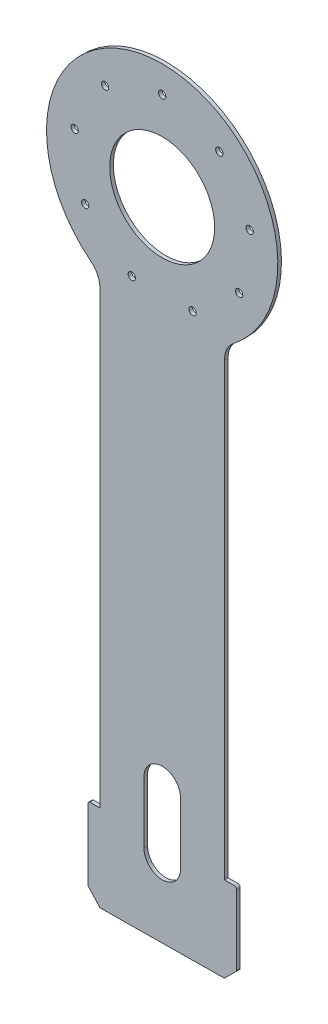
SolidWorks part; units mm, degrees
ref_plane "Front Plane" through (0, 0, 0) normal (0, 0, 1) x (1, 0, 0)
ref_plane "Top Plane" through (0, 0, 0) normal (0, 1, 0) x (1, 0, 0)
ref_plane "Right Plane" through (0, 0, 0) normal (1, 0, 0) x (0, 0, -1)
sketch "Sketch1" plane through (0, 0, 0) normal (0, 0, 1) x (1, 0, 0)
  circle A0 centre (0, 0) radius 47.5
  circle A1 centre (0, 0) radius 21.55
  dimension "D1" = 95
  dimension "D2" = 43.1
extrude "Boss-Extrude1" add sketch "Sketch1" along normal blind 1.5
sketch "Sketch2" plane through (0, 0, 1.5) normal (0, 0, 1) x (1, 0, 0)
  circle A0 centre (0, 0) radius 36.5 construction
  dimension "D1" = 73
sketch "Sketch3" plane through (0, 0, 1.5) normal (0, 0, 1) x (1, 0, 0)
  circle A0 centre (0, 36.5) radius 1.5
  circle A1 centre (0, 0) radius 36.5 construction
  point P0 (0, 36.5)
  dimension "D1" = 3
hole_wizard "Ø3.0mm Dowel Hole1" positions "Sketch3" profile "Sketch4" hole size "Ø3.0" standard "ANSI Metric" end condition through all
sketch "Sketch4" plane through (0, 36.5, 1.5) normal (1, 0, 0) x (0, -1, 0)
  line L0 (0, 0) -> (0, 1.5)
  line L1 (0, 1.5) -> (1.5, 1.5)
  line L2 (1.5, 1.5) -> (1.5, 0)
  line L5 (1.5, 0) -> (0, 0)
  line L11 (0, -6.35) -> (0, 107.95) construction
  dimension "Thru Hole Dia." = 3
  dimension "Thru Hole Depth" = 1.5
pattern_circular "CirPattern1" count 9 over 360 about axis through (0, 0, 1.5) along (0, 0, 1) of "Ø3.0mm Dowel Hole1"
sketch "Sketch6" plane through (0, 0, 1.5) normal (0, 0, 1) x (1, 0, 0)
  line L0 (0, -47.5) -> (0, -40.0345) construction
  line L1 (0, -40.0345) -> (-25.5634, -40.0345) construction
  line L2 (-25.5634, -40.0345) -> (25.5634, -40.0345) construction
  line L3 (-25.5634, -40.0345) -> (25.5634, -40.0345)
  line L4 (-25.5634, -40.0345) -> (-25.5634, -230.0345)
  line L5 (-25.5634, -230.0345) -> (-30.5634, -230.0345)
  line L6 (-30.5634, -230.0345) -> (-30.5634, -260.0345)
  line L7 (-30.5634, -260.0345) -> (-25.5634, -265.5368)
  line L8 (30.5634, -230.0345) -> (30.5634, -260.0345)
  line L9 (25.5634, -40.0345) -> (25.5634, -230.0345)
  line L10 (25.5634, -230.0345) -> (30.5634, -230.0345)
  line L11 (30.5634, -260.0345) -> (25.5634, -265.0345)
  line L12 (25.5634, -265.0345) -> (-25.5634, -265.5368)
  circle A1 centre (0, 0) radius 47.5 construction
extrude "Boss-Extrude2" add sketch "Sketch6" against normal blind 1.5
fillet "Fillet7" radius 10 1 edges at (-25.5634, -40.0345, 0.75)
fillet "Fillet8" radius 10 1 edges at (25.5634, -40.0345, 0.75)
fillet "Fillet9" radius 1 2 edges at (-30.5634, -230.0345, 0.75) (30.5634, -230.0345, 0.75)
fillet "Fillet10" radius 1 4 edges at (-30.5634, -260.0345, 0.75) (-25.5634, -265.5368, 0.75) (25.5634, -265.0345, 0.75) (30.5634, -260.0345, 0.75)
sketch "Sketch7" plane through (0, 0, 0) normal (0, 0, -1) x (-1, 0, 0)
  line L0 (-0.02, -265.2854) -> (-0.02, -235.2854) construction
  line L2 (25.1151, -265.5324) -> (-25.155, -265.0385) construction
  line L3 (-0.02, -235.2854) -> (-0.02, -209.8854) construction
  line L4 (-7.52, -235.2854) -> (-7.52, -209.8854)
  line L5 (7.48, -235.2854) -> (7.48, -209.8854)
  arc A0 (-7.52, -235.2854) -> (7.48, -235.2854) centre (-0.02, -235.2854) ccw
  arc A1 (7.48, -209.8854) -> (-7.52, -209.8854) centre (-0.02, -209.8854) ccw
  point P4 (-0.02, -222.5854)
extrude "Cut-Extrude1" cut sketch "Sketch7" against normal blind 1.5
